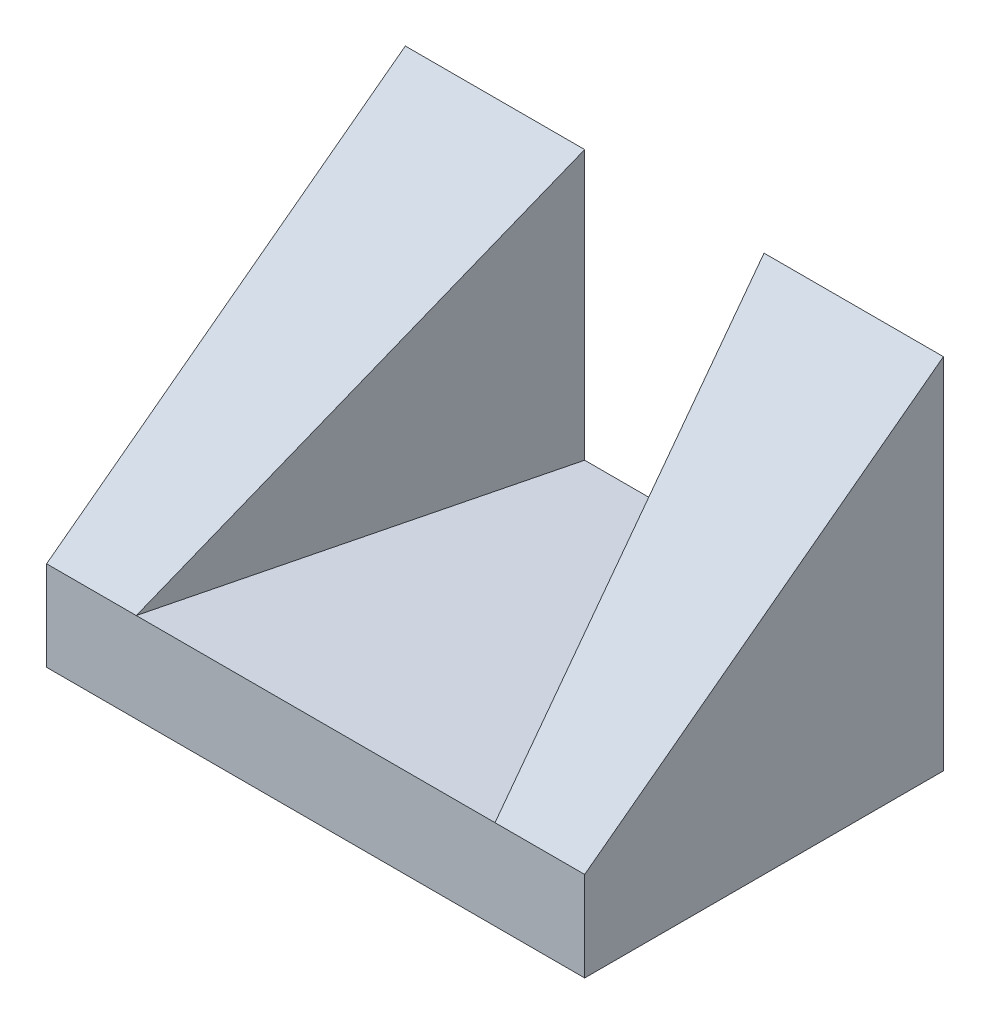
SolidWorks part; units mm, degrees
ref_plane "前基準面" through (0, 0, 0) normal (0, 0, 1) x (1, 0, 0)
ref_plane "上基準面" through (0, 0, 0) normal (0, 1, 0) x (1, 0, 0)
ref_plane "右基準面" through (0, 0, 0) normal (1, 0, 0) x (0, 0, -1)
sketch "草圖1" plane through (0, 0, 0) normal (0, 1, 0) x (1, 0, 0)
  line L0 (-5, 10) -> (-10, -10)
  line L1 (-15, -10) -> (15, -10)
  line L2 (-15, -10) -> (-15, 10)
  line L3 (-15, 10) -> (15, 10)
  line L4 (15, -10) -> (15, 10)
  line L5 (-15, -10) -> (15, 10) construction
  line L6 (-15, 10) -> (15, -10) construction
  line L7 (0, 14.0822) -> (0, -14.3444) construction
  line L8 (5, 10) -> (10, -10)
  point P0 (0, 0)
  dimension "D1" = 30
  dimension "D2" = 20
  dimension "D3" = 5
  dimension "D4" = 10
extrude "填料-伸長1" add sketch "草圖1" along normal blind 5 contours L3 L2 L1 L0 | L8 L3 L0 L1 | L3 L8 L1 L4 region at (0, 0, 1.1111) region at (-11.1111, 0, -1.1111) region at (11.1111, 0, -1.1111)
extrude "填料-伸長2" add sketch "草圖1<3>" along normal blind 20 contours L3 L2 L1 L0 | L3 L8 L1 L4 region at (-11.1111, 0, -1.1111) region at (11.1111, 0, -1.1111)
sketch "草圖1<3>" plane through (0, 0, 0) normal (0, 1, 0) x (1, 0, 0) same geometry as "草圖1"
sketch "草圖2" plane through (15, 0, 0) normal (1, 0, 0) x (0, 0, -1)
  line L0 (10, 20) -> (-10, 5)
  line L1 (-10, 20) -> (-10, 0) construction
  line L5 (-10, 5) -> (-10, 20)
  line L6 (-10, 20) -> (10, 20) construction
  line L7 (-10, 20) -> (10, 20)
extrude "除料-伸長1" cut sketch "草圖2" against normal blind 45
